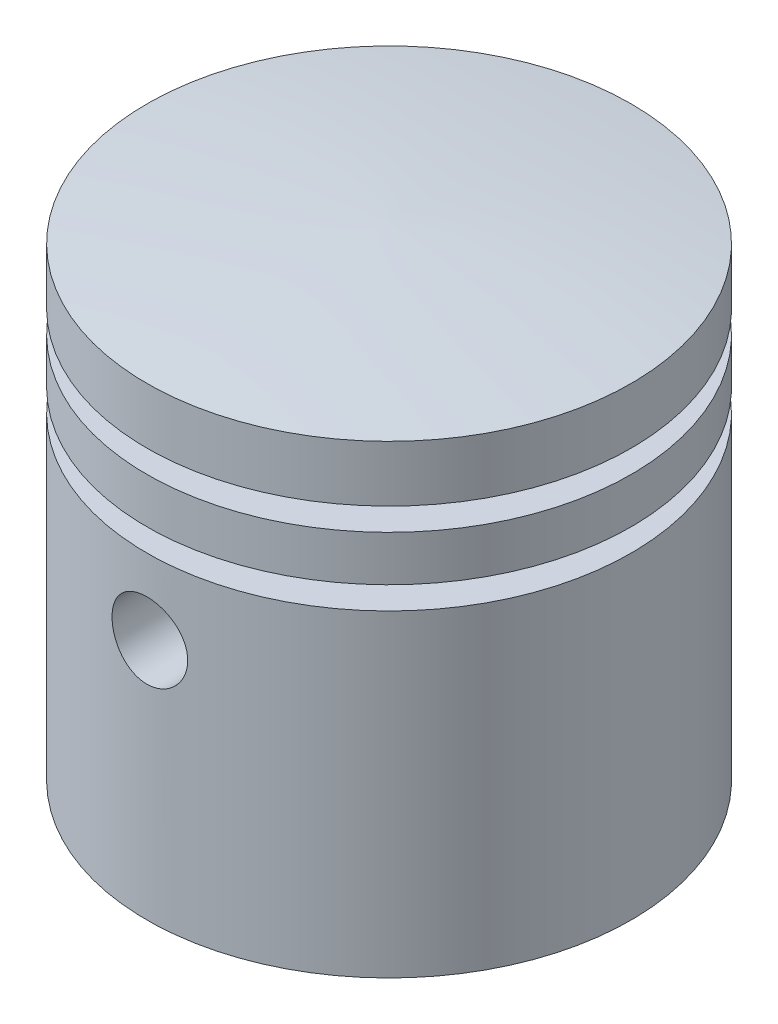
SolidWorks part; units mm, degrees
ref_plane "Front Plane" through (0, 0, 0) normal (0, 0, 1) x (1, 0, 0)
ref_plane "Top Plane" through (0, 0, 0) normal (0, 1, 0) x (1, 0, 0)
ref_plane "Right Plane" through (0, 0, 0) normal (1, 0, 0) x (0, 0, -1)
sketch "Sketch1" plane through (0, 0, 0) normal (1, 0, 0) x (0, 0, -1)
  line L1 (-16, 30.7073) -> (-16, 27)
  line L2 (-16, 27) -> (-12.5137, 27)
  line L3 (-12.5137, 27) -> (-12.5137, 25.5)
  line L4 (-12.5137, 25.5) -> (-16, 25.5)
  line L5 (-16, 25.5) -> (-16, 22.5)
  line L6 (-16, 22.5) -> (-12.5137, 22.5)
  line L7 (-12.5137, 22.5) -> (-12.5137, 21)
  line L8 (-12.5137, 21) -> (-16, 21)
  line L9 (-16, 21) -> (-16, 0)
  line L10 (-16, 0) -> (0, 0)
  line L11 (0, 0) -> (0, 32)
  arc A0 (-16, 30.7073) -> (0, 32) centre (5.0755, -130.4815) cw
  point P2 (-14.2569, 25.5)
  point P15 (-16, 29.7593)
  point P16 (-16, 30.7073)
  dimension "D2" = 1.5
  dimension "D3" = 1.5
  dimension "D4" = 3
  dimension "D5" = 32
  dimension "D6" = 16
  dimension "D7" = 21
revolve "Revolve1" add sketch "Sketch1" angle 360 about L11
sketch "Sketch2" plane through (0, 0, 0) normal (0, -1, 0) x (1, 0, 0)
  circle A0 centre (0, 0) radius 13
  circle A1 centre (0, 0) radius 10
  dimension "D1" = 26
  dimension "D2" = 20
extrude "Cut-Extrude1" cut sketch "Sketch2" against normal blind 10 contours A0
extrude "Cut-Extrude2" cut sketch "Sketch2<3>" against normal blind 24 contours A1 region at (0, 0, 0)
sketch "Sketch2<3>" plane through (0, 0, 0) normal (0, -1, 0) x (1, 0, 0) same geometry as "Sketch2"
sketch "Sketch3" plane through (0, 0, 0) normal (0, 0, 1) x (1, 0, 0)
  circle A0 centre (0, 16) radius 2.5
  point P2 (0, 0)
  dimension "D1" = 5
  dimension "D2" = 16
extrude "Cut-Extrude3" cut sketch "Sketch3" against normal through all both and the other way through all
